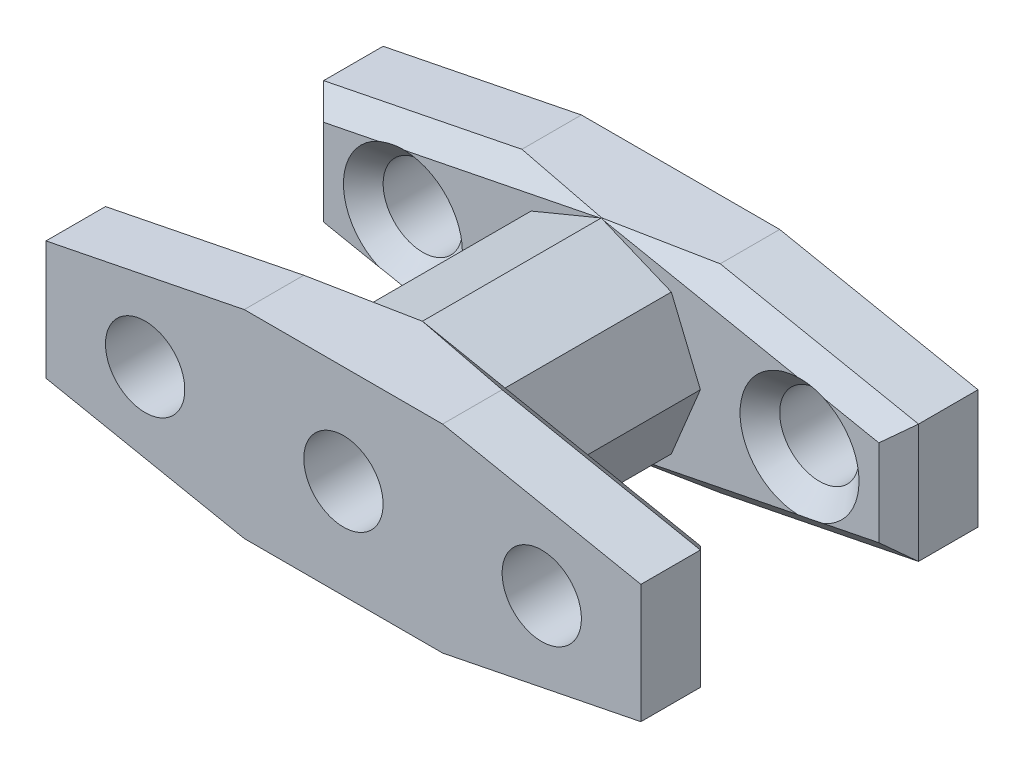
SolidWorks part; units mm, degrees
ref_plane "前视基准面" through (0, 0, 0) normal (0, 0, 1) x (1, 0, 0)
ref_plane "上视基准面" through (0, 0, 0) normal (0, 1, 0) x (1, 0, 0)
ref_plane "右视基准面" through (0, 0, 0) normal (1, 0, 0) x (0, 0, -1)
sketch "草图1" plane through (0, 0, 0) normal (0, 0, 1) x (1, 0, 0)
  line L0 (0, 0) -> (50000, 0) construction
  line L1 (15, -3) -> (15, 3)
  line L2 (15, 3) -> (5, 5)
  line L3 (5, 5) -> (-5, 5)
  line L4 (0, -55) -> (0, 55) construction
  line L5 (0, 0) -> (-50000, 0) construction
  line L6 (-15, 3) -> (-5, 5)
  line L7 (-15, -3) -> (-15, 3)
  line L8 (-15, -3) -> (-5, -5)
  line L9 (5, -5) -> (-5, -5)
  line L10 (15, -3) -> (5, -5)
  point P3 (15, 3.2442)
  point P12 (0, 5)
  point P13 (15, 0)
  point P18 (0, -5)
  point P19 (-15, 0)
  dimension "D1" = 10
  dimension "D2" = 15
  dimension "D3" = 5
  dimension "D4" = 2
extrude "凸台-拉伸1" add sketch "草图1" along normal blind 4
sketch "草图2" plane through (0, 0, 0) normal (0, 0, -1) x (-1, 0, 0)
  line L0 (-5, 5) -> (5, 5) construction
  line L1 (0, 5) -> (-3.5355, 3.5355)
  line L2 (-3.5355, 3.5355) -> (-5, 0)
  line L3 (-5, 0) -> (-3.5355, -3.5355)
  line L4 (-3.5355, -3.5355) -> (0, -5)
  line L5 (0, -5) -> (3.5355, -3.5355)
  line L6 (3.5355, -3.5355) -> (5, 0)
  line L7 (5, 0) -> (3.5355, 3.5355)
  line L8 (3.5355, 3.5355) -> (0, 5)
  circle A0 centre (0, 0) radius 4.6194 construction
  point P1 (0, 5)
extrude "凸台-拉伸2" add sketch "草图2" along normal blind 9
ref_plane "基准面1" through (0, 0, -4.5) normal (0, 0, -1) x (-1, 0, 0)
mirror "镜向1" about plane through (0, 0, -4.5) normal (0, 0, -1) of "凸台-拉伸1"
chamfer "倒角1" distance 1 angle 45 3 edges at (-10, -4, 0) (-15, 0, 0) (-10, 4, 0)
chamfer "倒角2" distance 1 angle 45 3 edges at (10, -4, 0) (15, 0, 0) (10, 4, 0)
chamfer "倒角3" distance 1 angle 45 3 edges at (-10, -4, -9) (-15, 0, -9) (-10, 4, -9)
chamfer "倒角4" distance 1 angle 45 3 edges at (10, -4, -9) (15, 0, -9) (10, 4, -9)
sketch "草图4" plane through (0, 0, -13) normal (0, 0, -1) x (-1, 0, 0)
  line L0 (0, 0) -> (10, 0) construction
  line L1 (0, 5.5) -> (0, -5.5) construction
  circle A0 centre (0, 0) radius 2
  circle A1 centre (10, 0) radius 2
  circle A2 centre (-10, 0) radius 2
  dimension "D1" = 4
  dimension "D2" = 10
extrude "切除-拉伸1" cut sketch "草图4" against normal through all both and the other way through all contours A2 | A0 | A1
chamfer "倒角5" distance 1 angle 45 4 edges at (-8, 0, -9) (12, 0, -9) (-12, 0, 0) (8, 0, 0)
